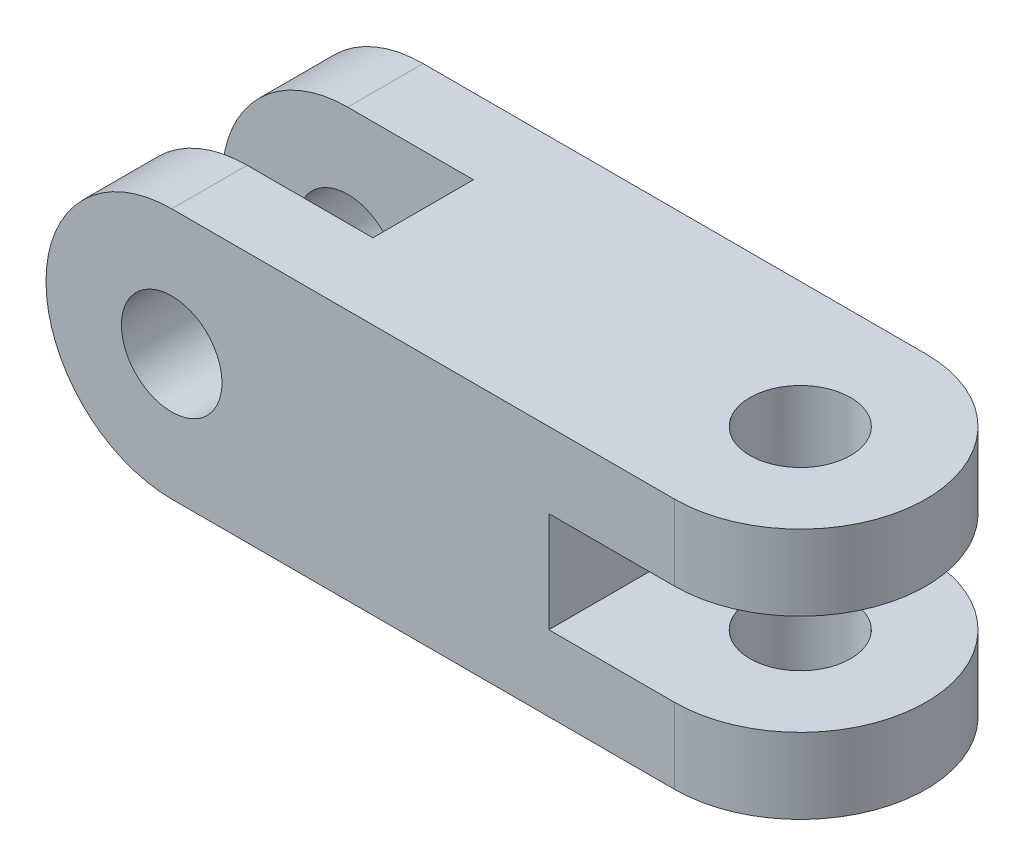
SolidWorks part; units mm, degrees
ref_plane "Front Plane" through (0, 0, 0) normal (0, 0, 1) x (1, 0, 0)
ref_plane "Top Plane" through (0, 0, 0) normal (0, 1, 0) x (1, 0, 0)
ref_plane "Right Plane" through (0, 0, 0) normal (1, 0, 0) x (0, 0, -1)
sketch "Sketch1" plane through (0, 0, 0) normal (0, 1, 0) x (1, 0, 0)
  line L0 (-78.5, -15.1884) -> (-78.5, -30.1884)
  line L1 (46.5, 19.8116) -> (-78.5, 19.8116)
  line L3 (46.5, -30.1884) -> (-78.5, -30.1884)
  line L4 (-78.5, 19.8116) -> (-78.5, 4.8116)
  line L5 (-78.5, 4.8116) -> (-28.5, 4.8116)
  line L7 (-78.5, -15.1884) -> (-28.5, -15.1884)
  line L8 (-28.5, 4.8116) -> (-28.5, -15.1884)
  circle A0 centre (46.5, -5.1884) radius 10
  arc A1 (46.5, -30.1884) -> (46.5, 19.8116) centre (46.5, -5.1884) ccw
  dimension "D2" = 25
  dimension "D3" = 20
  dimension "D1" = 50
  dimension "D4" = 20
  dimension "D5" = 125
  dimension "D6" = 15
  dimension "D7" = 15
extrude "Boss-Extrude1" add sketch "Sketch1" along normal blind 50
sketch "Sketch2" plane through (0, 0, 30.1884) normal (0, 0, 1) x (1, 0, 0)
  line L0 (71.5, 0) -> (71.5, 50) construction
  line L1 (71.5, 35) -> (21.5, 35)
  line L2 (71.5, 35) -> (71.5, 15)
  line L3 (71.5, 15) -> (21.5, 15)
  line L4 (21.5, 35) -> (21.5, 15)
  line L5 (71.5, 50) -> (46.5, 50) construction
  dimension "D1" = 20
  dimension "D2" = 15
  dimension "D3" = 50
extrude "Cut-Extrude1" cut sketch "Sketch2" against normal through all
fillet "Fillet1" radius 25 1 edges at (-78.5, 0, -12.3116) type face fillet first side face at (-78.5, 25, -12.3116) second side face at (-31.625, 0, 5.1884)
fillet "Fillet2" radius 25 1 edges at (-78.5, 0, 22.6884) type face fillet first side face at (-78.5, 25, 22.6884) second side face at (-25.375, 0, 5.1884)
fillet "Fillet3" radius 25 1 edges at (-78.5, 50, 22.6884) type face fillet first side face at (-31.625, 50, 5.1884) second side face at (-78.5, 37.5, 22.6884)
fillet "Fillet4" radius 25 1 edges at (-78.5, 50, -12.3116) type face fillet first side face at (-25.375, 50, 5.1884) second side face at (-78.5, 37.5, -12.3116)
sketch "Sketch3" plane through (0, 0, -19.8116) normal (0, 0, -1) x (-1, 0, 0)
  line L0 (-71.5, 50) -> (-71.5, 35) construction
  circle A0 centre (53.5, 25) radius 10
  point P2 (0, 0)
  dimension "D1" = 20
  dimension "D2" = 125
extrude "Cut-Extrude2" cut sketch "Sketch3" against normal through all
